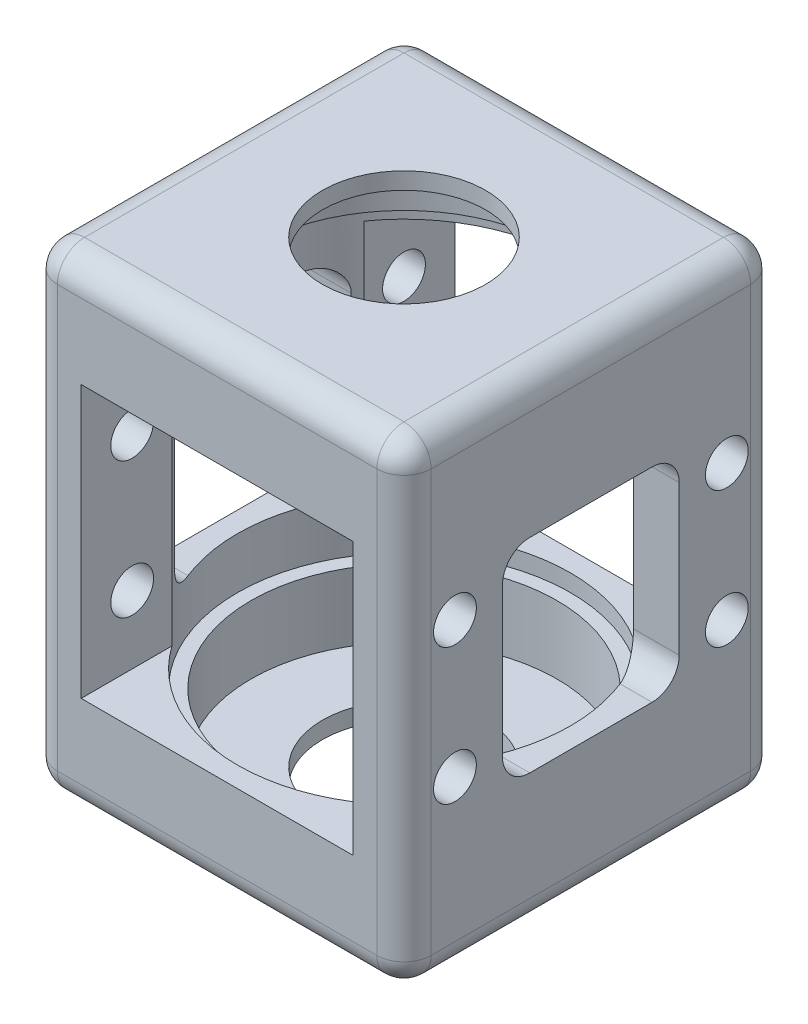
SolidWorks part; units mm, degrees
ref_plane "Front Plane" through (0, 0, 0) normal (0, 0, 1) x (1, 0, 0)
ref_plane "Top Plane" through (0, 0, 0) normal (0, 1, 0) x (1, 0, 0)
ref_plane "Right Plane" through (0, 0, 0) normal (1, 0, 0) x (0, 0, -1)
sketch "Sketch1" plane through (0, 0, 0) normal (0, 1, 0) x (1, 0, 0)
  line L1 (-17.4625, -17.4625) -> (17.4625, -17.4625)
  line L2 (-17.4625, -17.4625) -> (-17.4625, 17.4625)
  line L3 (-17.4625, 17.4625) -> (17.4625, 17.4625)
  line L4 (17.4625, -17.4625) -> (17.4625, 17.4625)
  line L5 (-17.4625, -17.4625) -> (17.4625, 17.4625) construction
  line L6 (-17.4625, 17.4625) -> (17.4625, -17.4625) construction
  circle A0 centre (0, 0) radius 7.62
  point P0 (0, 0)
  dimension "D3" = 15.24
  dimension "D1" = 34.925
  dimension "D2" = 34.925
extrude "Boss-Extrude1" add sketch "Sketch1" along normal blind 44.45
sketch "Sketch2" plane through (0, 0, 17.4625) normal (0, 0, 1) x (1, 0, 0)
  line L0 (-17.4625, 44.45) -> (-17.4625, 0) construction
  line L1 (12.7, 9.525) -> (-12.7, 9.525)
  line L2 (12.7, 9.525) -> (12.7, 34.925)
  line L3 (12.7, 34.925) -> (-12.7, 34.925)
  line L4 (-12.7, 9.525) -> (-12.7, 34.925)
  line L5 (12.7, 9.525) -> (-12.7, 34.925) construction
  line L6 (12.7, 34.925) -> (-12.7, 9.525) construction
  line L7 (-17.4625, 0) -> (17.4625, 0) construction
  point P0 (0, 22.225)
  dimension "D1" = 25.4
  dimension "D2" = 25.4
  dimension "D3" = 4.7625
  dimension "D4" = 9.525
extrude "Cut-Extrude1" cut sketch "Sketch2" against normal blind 44.45
sketch "Sketch3" plane through (0, 9.525, 0) normal (0, 1, 0) x (1, 0, 0)
  circle A0 centre (0, 0) radius 15.5575
  dimension "D1" = 31.115
extrude "Cut-Extrude2" cut sketch "Sketch3" against normal blind 1.6002 and the other way blind 27.0002
sketch "Sketch4" plane through (0, 7.9248, 0) normal (0, 1, 0) x (1, 0, 0)
  circle A0 centre (0, 0) radius 14.2875
  dimension "D1" = 28.575
extrude "Cut-Extrude3" cut sketch "Sketch4" against normal blind 6.35 and the other way blind 34.9504
sketch "Sketch5" plane through (-17.4625, 0, 0) normal (-1, 0, 0) x (0, 0, 1)
  line L0 (-17.4625, 44.45) -> (17.4625, 44.45) construction
  line L1 (-8.255, 12.7) -> (8.255, 12.7)
  line L2 (-8.255, 12.7) -> (-8.255, 31.75)
  line L3 (-8.255, 31.75) -> (8.255, 31.75)
  line L4 (8.255, 12.7) -> (8.255, 31.75)
  line L5 (-8.255, 12.7) -> (8.255, 31.75) construction
  line L6 (-8.255, 31.75) -> (8.255, 12.7) construction
  line L9 (-17.4625, 44.45) -> (-17.4625, 0) construction
  point P0 (0, 22.225)
  dimension "D1" = 16.51
  dimension "D2" = 19.05
  dimension "D3" = 12.7
  dimension "D4" = 9.2075
extrude "Cut-Extrude4" cut sketch "Sketch5" against normal blind 228.6
sketch "Sketch6" plane through (-17.4625, 0, 0) normal (-1, 0, 0) x (0, 0, 1)
  line L6 (-17.4625, 0) -> (17.4625, 0) construction
  line L7 (0, 44.45) -> (0, 0) construction
  line L8 (-17.4625, 44.45) -> (17.4625, 44.45) construction
  circle A0 centre (-12.7, 28.575) radius 2
  circle A1 centre (-12.7, 15.875) radius 2
  circle A2 centre (12.7, 15.875) radius 2
  circle A3 centre (12.7, 28.575) radius 2
  dimension "D3" = 4
  dimension "D1" = 12.7
  dimension "D2" = 15.875
  dimension "D4" = 12.7
  dimension "D5" = 12.7
extrude "Cut-Extrude5" cut sketch "Sketch6" against normal blind 228.6
fillet "Fillet1" radius 2.54 20 edges at (15.3246, 12.7, 8.255) (15.3246, 12.7, -8.255) (15.3246, 31.75, 8.255) (15.3246, 31.75, -8.255) (-17.4625, 0, 0) (-17.4625, 22.225, 17.4625) (0, 44.45, 17.4625) (17.4625, 44.45, 0) (17.4625, 22.225, 17.4625) (0, 0, 17.4625) (0, 0, -17.4625) (17.4625, 0, 0) (17.4625, 22.225, -17.4625) (-17.4625, 22.225, -17.4625) (0, 44.45, -17.4625) (-17.4625, 44.45, 0) (-15.3246, 12.7, -8.255) (-15.3246, 12.7, 8.255) (-15.3246, 31.75, 8.255) (-15.3246, 31.75, -8.255)
